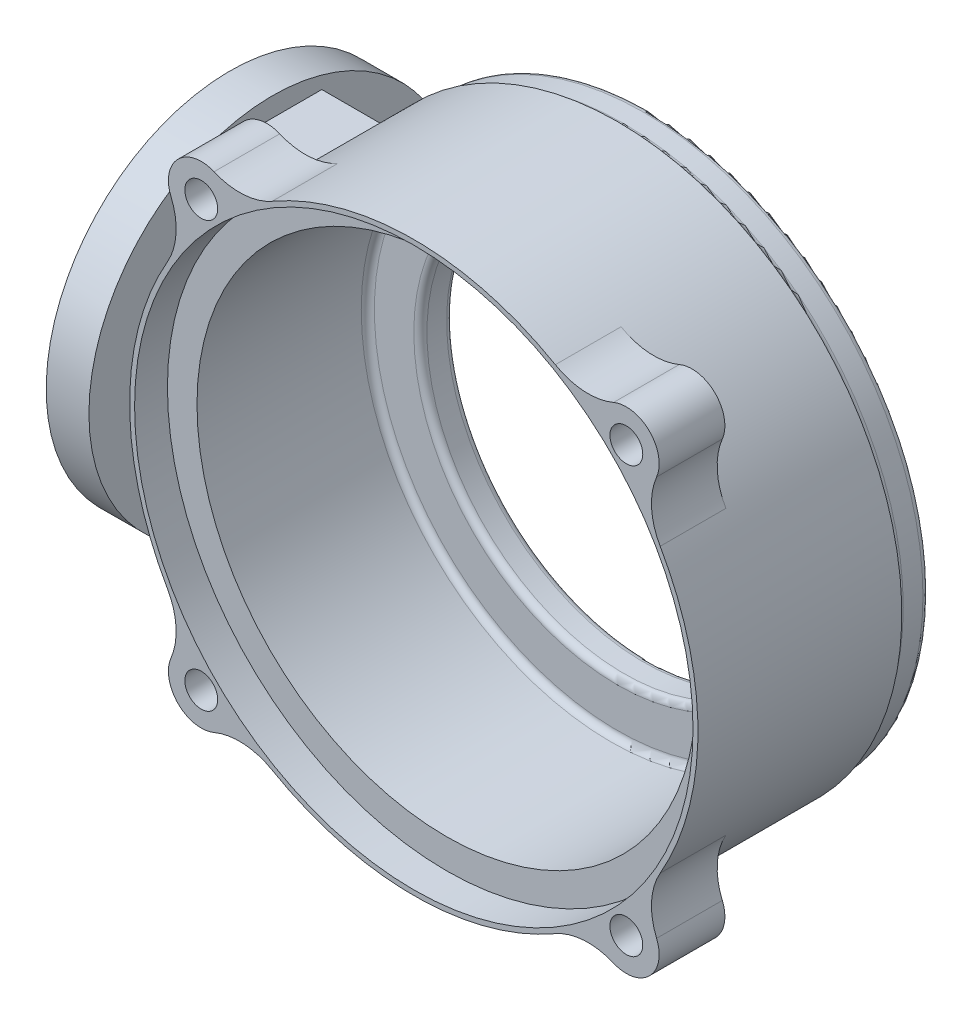
SolidWorks part; units mm, degrees
ref_plane "Front Plane" through (0, 0, 0) normal (0, 0, 1) x (1, 0, 0)
ref_plane "Top Plane" through (0, 0, 0) normal (0, 1, 0) x (1, 0, 0)
ref_plane "Right Plane" through (0, 0, 0) normal (1, 0, 0) x (0, 0, -1)
sketch "Sketch1" plane through (0, 0, 0) normal (0, 0, 1) x (1, 0, 0)
  line L0 (0, 0) -> (-45, 0) construction
  line L4 (0, 43.25) -> (-45, 43.25) construction
  line L5 (-45, 43.25) -> (-45, -43.25) construction
  line L6 (0, -43.25) -> (-45, -43.25) construction
  line L7 (-35.2925, 25) -> (-45, 25)
  line L8 (-45, 25) -> (-45, -25)
  line L9 (-35.2925, -25) -> (-45, -25)
  circle A0 centre (0, 0) radius 38
  arc A1 (0, -43.25) -> (0, 43.25) centre (0, 0) ccw construction
  arc A2 (-35.2925, -25) -> (-35.2925, 25) centre (0, 0) ccw
  dimension "D1" = 76
  dimension "D2" = 43.25
  dimension "D4" = 50
  dimension "D3" = 45
extrude "Boss-Extrude1" add sketch "Sketch1" along normal blind 40
sketch "Sketch6" plane through (0, 0, 0) normal (0, 0, -1) x (-1, 0, 0)
  circle A0 centre (0, 0) radius 99.6758
extrude "Cut-Extrude3" cut sketch "Sketch6" against normal mid plane 40
sketch "Sketch7" plane through (0, 0, 20) normal (0, 0, 1) x (1, 0, 0)
  circle A1 centre (0, 0) radius 42.5
  circle A2 centre (0, 0) radius 30
  dimension "D1" = 60
  dimension "D2" = 85
extrude "Boss-Extrude4" add sketch "Sketch7" against normal blind 5
fillet "Fillet1" radius 1 5 edges at (42.5, 0, 15) (30, 0, 15) (-38, 0, 20) (30, 0, 20) (42.5, 0, 20)
sketch "Sketch8" plane through (-45, 0, 0) normal (-1, 0, 0) x (0, 0, 1)
  line L0 (27.5, 0) -> (27.5, 18.75) construction
  line L7 (27.5, 0) -> (46.25, 0) construction
  line L10 (15, 0) -> (40, 0) construction
  line L11 (15, 41.5) -> (15, -41.5) construction
  line L12 (40, 0) -> (15, 0) construction
  line L13 (27.5, 0) -> (27.5, 43.25) construction
  line L14 (40, 25) -> (40, -25) construction
  arc A13 (22.5046, -0.2152) -> (22.504, -0.1987) centre (27.5, 0) ccw construction
  arc A14 (22.504, -0.1987) -> (22.5046, -0.2152) centre (27.5, 0) ccw construction
  arc A15 (25.8502, 18.7248) -> (25.8502, 18.7215) centre (27.5, 18.75) ccw construction
  circle A31 centre (27.5, 18.75) radius 1.65
  circle A32 centre (27.5, 0) radius 5
  circle A33 centre (46.25, 0) radius 1.65
  circle A34 centre (27.5, -18.75) radius 1.65
  circle A35 centre (8.75, 0) radius 1.65
  circle A37 centre (27.5, 0) radius 27.9508
  point P7 (30.3176, 0)
  point P9 (0, 0)
  point P26 (0, 0)
  point P29 (27.5, 0)
  point P37 (-17.5, 0)
  dimension "D5" = 18.75
  dimension "D4" = 3.3
  dimension "D6" = 10
  dimension "D7" = 4
extrude "Boss-Extrude5" add sketch "Sketch8" along normal blind 6.5
ref_axis "Axis1" through (0, 0, 40) along (0, 0, -1)
sketch "Sketch9" plane through (0, 0, 0) normal (0, 1, 0) x (1, 0, 0)
  line L0 (0, -40) -> (0, -46) construction
  line L1 (0, -40) -> (0, -21) construction
  line L2 (0, -46) -> (42.5, -46) construction
  line L3 (42.5, -46) -> (42.5, -17.5) construction
  line L4 (42.5, -19) -> (42.5, -16) construction
  line L9 (-35.2925, -40) -> (43.25, -40) construction
  line L10 (38, -40) -> (38, -46)
  line L11 (43.25, -40) -> (43.25, -19.9682) construction
  line L12 (38, -40) -> (43.25, -40)
  line L14 (43.25, -40) -> (43.25, -51)
  line L15 (43.25, -51) -> (42.5, -51)
  line L16 (42.5, -51) -> (42.5, -46)
  line L17 (42.5, -46) -> (38, -46)
  point P12 (0, 0)
  dimension "D1" = 5.25
  dimension "D2" = 6
  dimension "D3" = 5
revolve "Revolve1" add sketch "Sketch9" angle 360 about L0
sketch "Sketch10" plane through (0, 0, 51) normal (0, 0, 1) x (1, 0, 0)
  line L0 (0, 0) -> (-32.3501, 32.3501) construction
  line L1 (-35.2925, 25) -> (-45, 25) construction
  line L2 (0, 0) -> (32.3501, 32.3501) construction
  line L3 (0, 0) -> (32.3501, -32.3501) construction
  line L4 (0, 0) -> (-32.3501, -32.3501) construction
  circle A2 centre (-32.3501, 32.3501) radius 2.5
  circle A3 centre (0, 0) radius 43.25 construction
  arc A7 (-27.3533, 32.5276) -> (-32.5276, 27.3533) centre (-32.3501, 32.3501) ccw
  arc A10 (-27.3533, 32.5276) -> (-32.5276, 27.3533) centre (0, 0) ccw
  circle A11 centre (32.3501, 32.3501) radius 2.5 [skipped]
  circle A12 centre (32.3501, -32.3501) radius 2.5 [skipped]
  circle A13 centre (-32.3501, -32.3501) radius 2.5 [skipped]
  circle A14 centre (0, 0) radius 42.5 construction
  circle A15 centre (32.3501, 32.3501) radius 2.5
  arc A16 (32.5276, 27.3533) -> (27.3533, 32.5276) centre (32.3501, 32.3501) ccw
  arc A17 (32.5276, 27.3533) -> (27.3533, 32.5276) centre (0, 0) ccw
  circle A18 centre (32.3501, -32.3501) radius 2.5
  arc A19 (27.3533, -32.5276) -> (32.5276, -27.3533) centre (32.3501, -32.3501) ccw
  arc A20 (27.3533, -32.5276) -> (32.5276, -27.3533) centre (0, 0) ccw
  circle A21 centre (-32.3501, -32.3501) radius 2.5
  arc A22 (-32.5276, -27.3533) -> (-27.3533, -32.5276) centre (-32.3501, -32.3501) ccw
  arc A23 (-32.5276, -27.3533) -> (-27.3533, -32.5276) centre (0, 0) ccw
  point P18 (0, 0)
  point P35 (0, 0)
  dimension "D1" = 45
  dimension "D2" = 5
  dimension "D4" = 10
  dimension "D3" = 4
  dimension "D5" = 4
extrude "Boss-Extrude6" add sketch "Sketch10" against normal blind 10
fillet "Fillet2" radius 10 8 edges at (-27.464, 33.411, 46) (-33.411, 27.464, 46) (27.464, 33.411, 46) (33.411, 27.464, 46) (-33.411, -27.464, 46) (-27.464, -33.411, 46) (27.464, -33.411, 46) (33.411, -27.464, 46)
